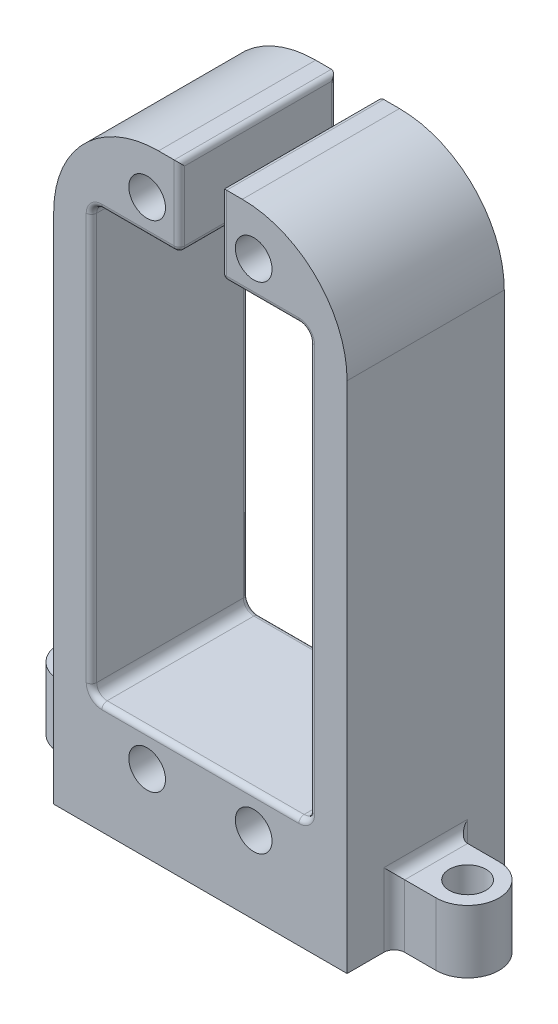
SolidWorks part; units mm, degrees
ref_plane "Front Plane" through (0, 0, 0) normal (0, 0, 1) x (1, 0, 0)
ref_plane "Top Plane" through (0, 0, 0) normal (0, 1, 0) x (1, 0, 0)
ref_plane "Right Plane" through (0, 0, 0) normal (1, 0, 0) x (0, 0, -1)
sketch "Sketch1" plane through (0, 0, 0) normal (0, 0, 1) x (1, 0, 0)
  line L1 (-5.085, -23.63) -> (5.085, -23.63) construction
  line L2 (-5.085, -23.63) -> (-5.085, 23.63) construction
  line L3 (-5.085, 23.63) -> (5.085, 23.63) construction
  line L4 (5.085, -23.63) -> (5.085, 23.63) construction
  line L5 (-5.085, -23.63) -> (5.085, 23.63) construction
  line L6 (-5.085, 23.63) -> (5.085, -23.63) construction
  line L7 (-10.4, -20.4) -> (10.4, -20.4)
  line L8 (-10.4, -20.4) -> (-10.4, 20.4)
  line L9 (-10.4, 20.4) -> (10.4, 20.4)
  line L10 (10.4, -20.4) -> (10.4, 20.4)
  line L11 (-10.4, -20.4) -> (10.4, 20.4) construction
  line L12 (-10.4, 20.4) -> (10.4, -20.4) construction
  line L13 (-14, -28) -> (14, -28)
  line L14 (-14, -28) -> (-14, 28)
  line L15 (-14, 28) -> (14, 28)
  line L16 (14, -28) -> (14, 28)
  line L17 (-14, -28) -> (14, 28) construction
  line L18 (-14, 28) -> (14, -28) construction
  circle A0 centre (-5.085, 23.63) radius 1.75
  circle A1 centre (5.085, 23.63) radius 1.75
  circle A2 centre (-5.085, -23.63) radius 1.75
  circle A3 centre (5.085, -23.63) radius 1.75
  point P0 (0, 0)
  point P10 (0, 0)
  point P15 (0, 0)
  dimension "D3" = 3.5
  dimension "D1" = 10.17
  dimension "D2" = 47.26
  dimension "D4" = 20.8
  dimension "D5" = 40.8
  dimension "D6" = 28
  dimension "D7" = 56
extrude "Boss-Extrude1" add sketch "Sketch1" along normal blind 15
fillet "Fillet1" radius 10 2 edges at (14, 28, 7.5) (-14, 28, 7.5)
fillet "Fillet2" radius 1 4 edges at (10.4, -20.4, 7.5) (-10.4, -20.4, 7.5) (-10.4, 20.4, 7.5) (10.4, 20.4, 7.5)
fillet "Fillet3" radius 0.5 16 edges at (10.1071, -20.1071, 0) (-10.1071, -20.1071, 0) (-10.1071, 20.1071, 0) (10.1071, 20.1071, 0) (10.1071, -20.1071, 15) (-10.1071, -20.1071, 15) (-10.1071, 20.1071, 15) (10.1071, 20.1071, 15) (0, -20.4, 0) (-10.4, 0, 0) (0, 20.4, 0) (10.4, 0, 0) (0, 20.4, 15) (-10.4, 0, 15) (0, -20.4, 15) (10.4, 0, 15)
sketch "Sketch2" plane through (0, -28, 0) normal (0, -1, 0) x (1, 0, 0)
  line L0 (14, 15) -> (14, 0) construction
  line L1 (18, 4.5) -> (14, 4.5)
  line L2 (14, 4.5) -> (14, 10.5)
  line L3 (14, 10.5) -> (18, 10.5)
  line L4 (0, -8.25) -> (0, 8.25) construction
  line L5 (-14, 4.5) -> (-14, 10.5)
  line L6 (-14, 10.5) -> (-18, 10.5)
  line L7 (-18, 4.5) -> (-14, 4.5)
  line L8 (-18, 7.5) -> (18, 7.5) construction
  line L9 (0, 15) -> (0, 0) construction
  line L10 (-14, 15) -> (14, 15) construction
  circle A0 centre (18, 7.5) radius 1.75
  circle A1 centre (18, 7.5) radius 3
  circle A2 centre (-18, 7.5) radius 3
  circle A3 centre (-18, 7.5) radius 1.75
  point P23 (0, 7.5)
  point P24 (0, 7.5)
  line M6 (14, 0) -> (14, 15)
  line M8 (-14, 15) -> (-14, 0)
  dimension "D1" = 3.5
  dimension "D2" = 6
  dimension "D3" = 4
extrude "Boss-Extrude2" add sketch "Sketch2" against normal blind 3 contours A2 A3 | L6 A2 L7 M8 | A1 L3 L1 M6 | A1 A0 region at (14.9583, -28, 7.5) region at (15.0849, -28, 7.5) region at (-14.9583, -28, 7.5) region at (-20.9151, -28, 7.5)
fillet "Fillet4" radius 1 2 edges at (-14, -25, 7.5) (14, -25, 7.5)
fillet "Fillet5" radius 1 4 edges at (14, -26, 10.5) (14, -26, 4.5) (-14, -26, 4.5) (-14, -26, 10.5)
sketch "Sketch3" plane through (0, -28, 0) normal (0, -1, 0) x (1, 0, 0)
  line L10 (-14, 0) -> (14, 0)
  line L11 (14, 0) -> (14, 3.5)
  line L12 (15, 4.5) -> (18, 4.5)
  line L13 (18, 10.5) -> (15, 10.5)
  line L14 (14, 11.5) -> (14, 15)
  line L15 (14, 15) -> (-14, 15)
  line L16 (-14, 15) -> (-14, 11.5)
  line L17 (-15, 10.5) -> (-18, 10.5)
  line L18 (-18, 4.5) -> (-15, 4.5)
  line L19 (-14, 3.5) -> (-14, 0)
  line L20 (-14, 0) -> (14, 0)
  line L21 (14, 0) -> (14, 3.5)
  line L22 (15, 4.5) -> (18, 4.5)
  line L23 (18, 10.5) -> (15, 10.5)
  line L24 (14, 11.5) -> (14, 15)
  line L25 (14, 15) -> (-14, 15)
  line L26 (-14, 15) -> (-14, 11.5)
  line L27 (-15, 10.5) -> (-18, 10.5)
  line L28 (-18, 4.5) -> (-15, 4.5)
  line L29 (-14, 3.5) -> (-14, 0)
  circle A0 centre (18, 7.5) radius 1.75 construction
  circle A1 centre (-18, 7.5) radius 1.75 construction
  circle A2 centre (18, 7.5) radius 1.75
  circle A3 centre (-18, 7.5) radius 1.75
  arc A6 (15, 4.5) -> (14, 3.5) centre (15, 3.5) ccw
  arc A7 (18, 4.5) -> (18, 10.5) centre (18, 7.5) ccw
  arc A8 (14, 11.5) -> (15, 10.5) centre (15, 11.5) ccw
  arc A9 (-15, 10.5) -> (-14, 11.5) centre (-15, 11.5) ccw
  arc A10 (-18, 10.5) -> (-18, 4.5) centre (-18, 7.5) ccw
  arc A11 (-14, 3.5) -> (-15, 4.5) centre (-15, 3.5) ccw
  arc A12 (15, 4.5) -> (14, 3.5) centre (15, 3.5) ccw
  arc A13 (18, 4.5) -> (18, 10.5) centre (18, 7.5) ccw
  arc A14 (14, 11.5) -> (15, 10.5) centre (15, 11.5) ccw
  arc A15 (-15, 10.5) -> (-14, 11.5) centre (-15, 11.5) ccw
  arc A16 (-18, 10.5) -> (-18, 4.5) centre (-18, 7.5) ccw
  arc A17 (-14, 3.5) -> (-15, 4.5) centre (-15, 3.5) ccw
  dimension "D1" = 0
extrude "Boss-Extrude3" add sketch "Sketch3" along normal blind 3
sketch "Sketch4" plane through (0, 0, 15) normal (0, 0, 1) x (1, 0, 0)
  line L0 (0, -8.25) -> (0, 8.25) construction
  line L1 (-2, 19.5124) -> (2, 19.5124)
  line L2 (-2, 19.5124) -> (-2, 28)
  line L3 (-2, 28) -> (2, 28)
  line L4 (2, 19.5124) -> (2, 28)
  line L5 (-2, 19.5124) -> (2, 28) construction
  line L6 (-2, 28) -> (2, 19.5124) construction
  line L7 (4, 28) -> (-4, 28) construction
  point P0 (0, 23.7562)
  dimension "D1" = 4
extrude "Cut-Extrude1" cut sketch "Sketch4" against normal up to surface (15 mm away) up to face at (0, 0, 0)
fillet "Fillet6" radius 0.5 12 edges at (-2, 20.5464, 14.8536) (-2, 20.5464, 0.1464) (2, 20.5464, 0.1464) (2, 20.5464, 14.8536) (-2, 24.45, 0) (2, 24.45, 0) (2, 24.45, 15) (-2, 24.45, 15) (-2, 20.4, 7.5) (2, 20.4, 7.5) (2, 28, 7.5) (-2, 28, 7.5)
